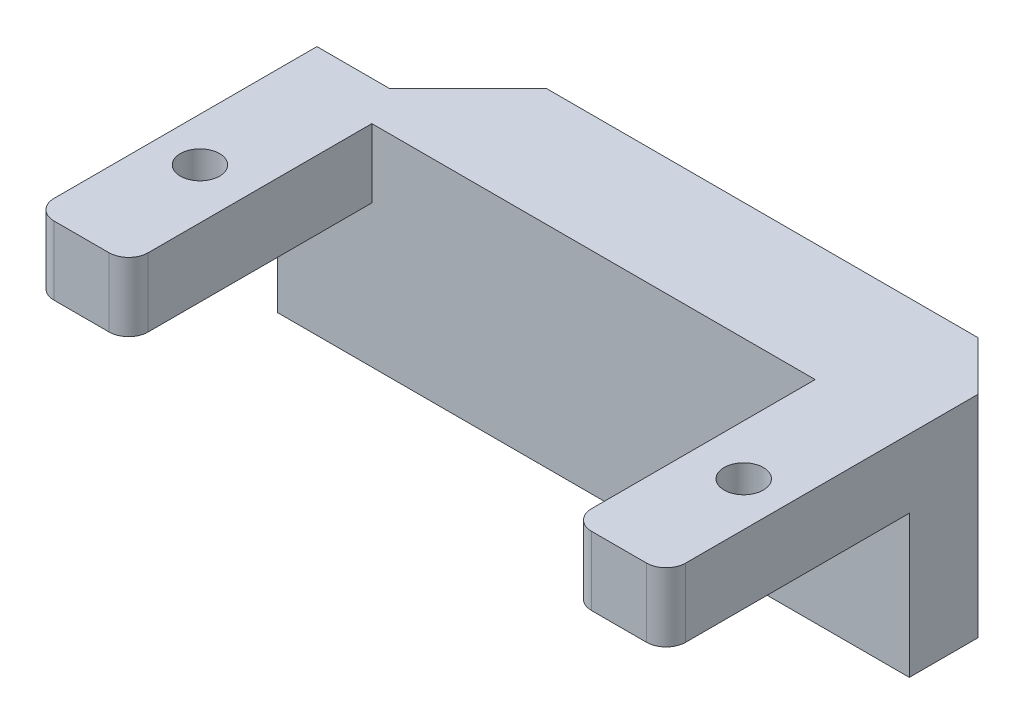
SolidWorks part; units mm, degrees
ref_plane "Front Plane" through (0, 0, 0) normal (0, 0, 1) x (1, 0, 0)
ref_plane "Top Plane" through (0, 0, 0) normal (0, 1, 0) x (1, 0, 0)
ref_plane "Right Plane" through (0, 0, 0) normal (1, 0, 0) x (0, 0, -1)
sketch "Sketch1" plane through (0, 0, 0) normal (0, 0, 1) x (1, 0, 0)
  line L1 (-16.1, 12.75) -> (16.1, 12.75)
  line L2 (-16.1, 12.75) -> (-16.1, -12.75)
  line L3 (-16.1, -12.75) -> (16.1, -12.75)
  line L4 (16.1, 12.75) -> (16.1, -12.75)
  line L5 (-16.1, 12.75) -> (16.1, -12.75) construction
  line L6 (-16.1, -12.75) -> (16.1, 12.75) construction
  point P0 (0, 0)
  dimension "D1" = 32.2
  dimension "D2" = 25.5
extrude "Boss-Extrude1" add sketch "Sketch1" along normal blind 14.4
sketch "Sketch3" plane through (0, 0, 14.4) normal (0, 0, 1) x (1, 0, 0)
  line L0 (-16.1, 12.75) -> (-16.1, -12.75) construction
  line L1 (-16.1, 10.75) -> (16.1, 10.75)
  line L2 (-16.1, 10.75) -> (-16.1, -11)
  line L3 (-16.1, -11) -> (16.1, -11)
  line L4 (16.1, 10.75) -> (16.1, -11)
  line L5 (16.1, -12.75) -> (16.1, 12.75) construction
  line L6 (16.1, 12.75) -> (-16.1, 12.75) construction
  dimension "D1" = 2
  dimension "D2" = 21.75
extrude "Cut-Extrude1" cut sketch "Sketch3" against normal blind 12.4
sketch "Sketch5" plane through (0, 0, 14.4) normal (0, 0, 1) x (1, 0, 0)
  line L0 (16.1, 12.75) -> (-16.1, 12.75) construction
  line L1 (-11.3, 12.75) -> (11.3, 12.75)
  line L2 (-11.3, 12.75) -> (-11.3, 10.75)
  line L3 (-11.3, 10.75) -> (11.3, 10.75)
  line L4 (11.3, 12.75) -> (11.3, 10.75)
  line L5 (16.1, 10.75) -> (-16.1, 10.75) construction
  line L6 (-16.1, 12.75) -> (-16.1, 10.75) construction
  line L7 (16.1, 10.75) -> (16.1, 12.75) construction
  dimension "D1" = 4.8
  dimension "D2" = 4.8
extrude "Cut-Extrude2" cut sketch "Sketch5" against normal blind 14.4 contours L2 L1 L4 L3
fillet "Fillet1" radius 1 1 edges at (-11.3, 11.75, 14.4)
fillet "Fillet2" radius 1 1 edges at (-16.1, 11.75, 14.4)
fillet "Fillet3" radius 1 1 edges at (11.3, 11.75, 14.4)
fillet "Fillet4" radius 1 1 edges at (16.1, 11.75, 14.4)
sketch "Sketch10" plane through (0, 12.75, 0) normal (0, 1, 0) x (1, 0, 0)
  line L0 (-16.1, -13.4) -> (-16.1, 0) construction
  circle A0 centre (-13.86, -8.203) radius 1
  dimension "D1" = 2.24
extrude "Cut-Extrude3" cut sketch "Sketch10" against normal blind 10
mirror "Mirror1" about plane through (0, 0, 0) normal (1, 0, 0) of "Cut-Extrude3"
sketch "Sketch11" plane through (0, 0, 14.4) normal (0, 0, 1) x (1, 0, 0)
  line L0 (-16.1, -12.75) -> (16.1, -12.75) construction
  line L1 (-16.1, -11) -> (-11.25, -11)
  line L2 (-16.1, -11) -> (-16.1, -12.75)
  line L3 (-16.1, -12.75) -> (-11.25, -12.75)
  line L4 (-11.25, -11) -> (-11.25, -12.75)
  dimension "D1" = 4.85
extrude "Cut-Extrude4" cut sketch "Sketch11" against normal blind 20
mirror "Mirror2" about plane through (0, 0, 0) normal (1, 0, 0) of "Cut-Extrude4"
fillet "Fillet5" radius 1 6 edges at (-11.25, -11.875, 0) (-16.1, -11, 1) (16.1, -11, 1) (11.25, -11.875, 0) (11.25, -11.875, 14.4) (-11.25, -11.875, 14.4)
sketch "Sketch12" plane through (0, 0, 0) normal (0, 0, -1) x (-1, 0, 0)
  line L1 (-12.6, 5.5) -> (7.4, 5.5)
  line L2 (-12.6, 5.5) -> (-12.6, 3.5)
  line L3 (-12.6, 3.5) -> (7.4, 3.5)
  line L4 (7.4, 5.5) -> (7.4, 3.5)
  line L6 (11.3, 10.75) -> (-11.3, 10.75) construction
  line L9 (-16.1, -10) -> (-16.1, 12.75) construction
  dimension "D1" = 5.25
  dimension "D2" = 2
  dimension "D3" = 20
  dimension "D4" = 3.5
extrude "Boss-Extrude2" add sketch "Sketch12" along normal blind 5
sketch "Sketch13" plane through (0, 0, 0) normal (0, 0, -1) x (-1, 0, 0)
  line L0 (7.4, 5.5) -> (-12.6, 5.5) construction
  line L1 (-12.6, 9) -> (7.4, 9)
  line L2 (-12.6, 9) -> (-12.6, 7)
  line L3 (-12.35, 7) -> (7.15, 7)
  line L4 (7.4, 9) -> (7.4, 7)
  line L5 (-2.6, 7) -> (-2.6, 5.5) construction
  line L7 (-12.6, 7) -> (-12.6, 5.5)
  line L8 (-12.6, 5.5) -> (-12.35, 5.5)
  line L9 (-12.35, 7) -> (-12.35, 5.5)
  line L10 (7.4, 5.5) -> (-12.6, 5.5) construction
  line L11 (7.4, 5.5) -> (7.15, 5.5)
  line L12 (7.15, 7) -> (7.15, 5.5)
  line L14 (7.4, 7) -> (7.4, 5.5)
  dimension "D1" = 1.5
  dimension "D2" = 0.25
extrude "Boss-Extrude3" add sketch "Sketch13" along normal blind 5
sketch "Sketch14" plane through (0, 3.5, 0) normal (0, -1, 0) x (1, 0, 0)
  line L1 (-19.2363, 15.8932) -> (18.6063, 15.8932)
  line L2 (-19.2363, 15.8932) -> (-19.2363, -6.2412)
  line L3 (-19.2363, -6.2412) -> (18.6063, -6.2412)
  line L4 (18.6063, 15.8932) -> (18.6063, -6.2412)
extrude "Cut-Extrude5" cut sketch "Sketch14" along normal through all
sketch "Sketch15" plane through (0, 12.75, 0) normal (0, 1, 0) x (1, 0, 0)
  line L0 (-7.4, 0) -> (12.6, 0) construction
  line L1 (12.6, 0) -> (12.6, 5) construction
  line L2 (12.6, 5) -> (-7.4, 5) construction
  line L3 (-7.4, 5) -> (-7.4, 0) construction
  line L4 (-11.3, -2) -> (11.3, -2) construction
  line L5 (11.3, -2) -> (11.3, 0) construction
  line L6 (11.3, 0) -> (-11.3, 0) construction
  line L7 (-11.3, 0) -> (-11.3, -2) construction
  line L8 (11.3, 0) -> (12.6, 0)
  line L9 (12.6, 0) -> (12.6, 5)
  line L10 (12.6, 5) -> (-7.4, 5)
  line L11 (-7.4, 5) -> (-7.4, 0)
  line L12 (-11.3, -2) -> (11.3, -2)
  line L13 (11.3, -2) -> (11.3, 0)
  line L14 (-7.4, 0) -> (-11.3, 0)
  line L15 (-11.3, 0) -> (-11.3, -2)
extrude "Boss-Extrude5" add sketch "Sketch15" against normal up to surface (3.75 mm away) up to face at (2.6, 9, -2.5)
chamfer "Chamfer1" distance 5 angle 45 2 edges at (-7.4, 8.125, 0) (12.6, 8.125, 0)
sketch "Sketch16" plane through (0, 12.75, 0) normal (0, 1, 0) x (1, 0, 0)
  line L11 (16.1, -13.4) -> (16.1, 1.5)
  line L12 (16.1, 1.5) -> (12.6, 5)
  line L13 (12.6, 5) -> (-7.4, 5)
  line L14 (-7.4, 5) -> (-12.4, 0)
  line L15 (-12.4, 0) -> (-16.1, 0)
  line L16 (-16.1, 0) -> (-16.1, -13.4)
  line L17 (-15.1, -14.4) -> (-12.3, -14.4)
  line L18 (-11.3, -13.4) -> (-11.3, -2)
  line L19 (-11.3, -2) -> (11.3, -2)
  line L20 (11.3, -2) -> (11.3, -13.4)
  line L21 (12.3, -14.4) -> (15.1, -14.4)
  line L22 (16.1, -13.4) -> (16.1, 1.5)
  line L23 (16.1, 1.5) -> (12.6, 5)
  line L24 (12.6, 5) -> (-7.4, 5)
  line L25 (-7.4, 5) -> (-12.4, 0)
  line L26 (-12.4, 0) -> (-16.1, 0)
  line L27 (-16.1, 0) -> (-16.1, -13.4)
  line L28 (-15.1, -14.4) -> (-12.3, -14.4)
  line L29 (-11.3, -13.4) -> (-11.3, -2)
  line L30 (-11.3, -2) -> (11.3, -2)
  line L31 (11.3, -2) -> (11.3, -13.4)
  line L32 (12.3, -14.4) -> (15.1, -14.4)
  circle A0 centre (13.86, -8.203) radius 1 construction
  circle A1 centre (-13.86, -8.203) radius 1 construction
  circle A2 centre (13.86, -8.203) radius 1
  circle A3 centre (-13.86, -8.203) radius 1
  arc A4 (-16.1, -13.4) -> (-15.1, -14.4) centre (-15.1, -13.4) ccw
  arc A5 (-12.3, -14.4) -> (-11.3, -13.4) centre (-12.3, -13.4) ccw
  arc A6 (11.3, -13.4) -> (12.3, -14.4) centre (12.3, -13.4) ccw
  arc A7 (15.1, -14.4) -> (16.1, -13.4) centre (15.1, -13.4) ccw
  arc A8 (-16.1, -13.4) -> (-15.1, -14.4) centre (-15.1, -13.4) ccw
  arc A9 (-12.3, -14.4) -> (-11.3, -13.4) centre (-12.3, -13.4) ccw
  arc A10 (11.3, -13.4) -> (12.3, -14.4) centre (12.3, -13.4) ccw
  arc A11 (15.1, -14.4) -> (16.1, -13.4) centre (15.1, -13.4) ccw
  dimension "D1" = 0
extrude "Boss-Extrude6" add sketch "Sketch16" along normal blind 1.5
sketch "Sketch17" plane through (0, 0, -5) normal (0, 0, -1) x (-1, 0, 0)
  line L1 (-18.3963, 20.4042) -> (13.5242, 20.4042)
  line L2 (-18.3963, 20.4042) -> (-18.3963, -1.8562)
  line L3 (-18.3963, -1.8562) -> (13.5242, -1.8562)
  line L4 (13.5242, 20.4042) -> (13.5242, -1.8562)
extrude "Cut-Extrude6" cut sketch "Sketch17" against normal blind 1
scale "Scale1" scale about centroid uniform scaling yes scale factor 1.02
